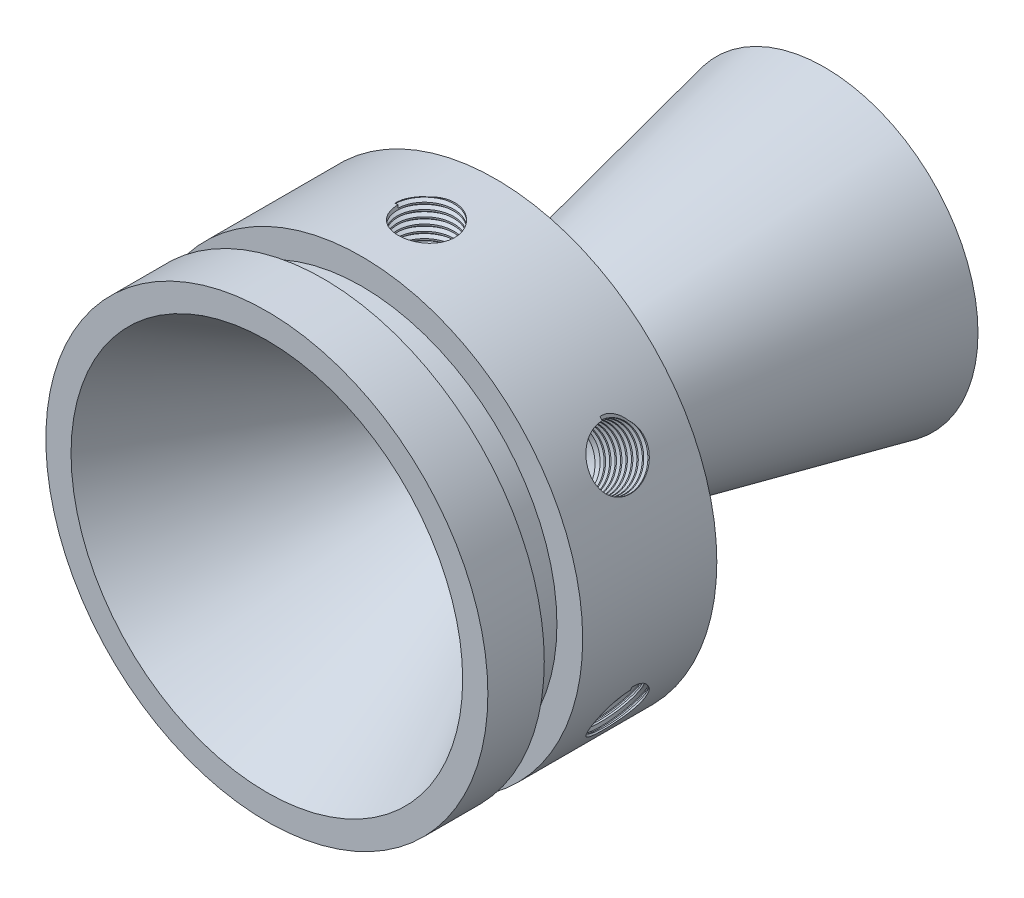
SolidWorks part; units mm, degrees
material "SAE 1018"
ref_plane "Alzado" through (0, 0, 0) normal (0, 0, 1) x (1, 0, 0)
ref_plane "Planta" through (0, 0, 0) normal (0, 1, 0) x (1, 0, 0)
ref_plane "Vista lateral" through (0, 0, 0) normal (1, 0, 0) x (0, 0, -1)
sketch "Croquis2" plane through (0, 0, 0) normal (1, 0, 0) x (0, 0, -1)
  line L0 (-14.0172, 0) -> (56.1534, 0) construction
  line L1 (0, 15.54) -> (17.4731, 5.4519)
  line L3 (0, 15.54) -> (0, 17.54)
  line L4 (0, 17.54) -> (4.476, 17.54)
  line L5 (18.1692, 17.54) -> (18.1692, 8.54)
  line L7 (44.264, 12.1715) -> (44.264, 10.1715)
  line L8 (4.476, 17.54) -> (4.476, 15.4951)
  line L9 (4.476, 15.4951) -> (7.524, 15.4951)
  line L10 (7.524, 15.4951) -> (7.524, 17.54)
  line L11 (7.524, 17.54) -> (18.1692, 17.54)
  line L12 (18.9731, 5.05) -> (19.6437, 5.05)
  line L13 (20.6833, 5.1593) -> (44.264, 10.1715)
  line L15 (20.1692, 7.05) -> (44.264, 12.1715)
  line L16 (19.1692, 7.3661) -> (19.1692, 4.8006) construction
  line L17 (20.1692, 7.05) -> (18.1692, 8.54)
  line L18 (16.3437, 6.104) -> (19.3157, 4.3881) construction
  line L19 (19.0363, 5.05) -> (17.4124, 5.05) construction
  line L20 (19.4766, 5.05) -> (20.8834, 5.05) construction
  line L21 (21.256, 5.281) -> (19.5107, 4.91) construction
  arc A0 (18.9731, 5.05) -> (17.4731, 5.4519) centre (18.9731, 8.05) cw
  arc A1 (19.6437, 5.05) -> (20.6833, 5.1593) centre (19.6437, 10.05) ccw
  point P14 (6, 15.4951)
  point P15 (12.6692, 17.54)
  point P19 (20.1692, 5.05)
  point P23 (18.1692, 5.05)
  point P30 (18.1692, 5.05)
  point P35 (20.1692, 5.05)
  dimension "D14" = 3
  dimension "D15" = 5
  dimension "D2" = 30
  dimension "D4" = 31.08
  dimension "D5" = 20.343
  dimension "D7" = 35.08
  dimension "D8" = 6
  dimension "D11" = 5.5
  dimension "D3" = 2
  dimension "D6" = 10.1
  dimension "D12" = 2
  dimension "D13" = 12
  dimension "D16" = 9
  dimension "D9" = 2.0449
  dimension "D10" = 3.048
revolve "Revolución1" add sketch "Croquis2" angle 360 about L0
ref_plane "Plano1" through (0, 17.54, 0) normal (0, 1, 0) x (1, 0, 0)
sketch "Croquis3" plane through (0, 17.54, 0) normal (0, 1, 0) x (1, 0, 0)
  line L0 (17.54, 18.1692) -> (-17.54, 18.1692) construction
  point P0 (0, 12.6692)
  dimension "D1" = 5.5
hole_wizard "M4 Clearance Hole1" positions "Croquis3" profile "Croquis5" hole size "M4" standard "ANSI Metric"
sketch "Croquis5" plane through (0, 17.54, -12.6692) normal (1, 0, 0) x (0, 0, 1)
  line L0 (0, 0) -> (0, 6.3519)
  line L1 (0, 6.3519) -> (2.25, 5)
  line L2 (2.25, 5) -> (2.25, 0)
  line L5 (2.25, 0) -> (0, 0)
  line L10 (0, 6.3519) -> (-2.25, 5) construction
  line L11 (0, -6.35) -> (0, 107.95) construction
  dimension "Diámetro de taladro" = 4.5
  dimension "Profundidad de taladro" = 5
  dimension "Ángulo de perforador" = 118
thread "Rosca1" pitch 0.5 start angle 0, offset 0, length 4.5, pitch 0.5, diameter 4.5
ref_plane "Plano2" through (-2.25, 17.54, -12.6692) normal (0, 0, 1) x (-1, 0, 0)
sketch "Perfil de rosca1" plane through (-2.25, 17.54, -12.6692) normal (0, 0, 1) x (-1, 0, 0)
  line L0 (0, 0) -> (0, 0.5) construction
  line L1 (0, 0) -> (0.2706, 0.1562)
  line L2 (0.2706, 0.1562) -> (0.2706, 0.2187)
  line L3 (0.2706, 0.2187) -> (0, 0.375)
  line L4 (0.2706, 0.1875) -> (0, 0.1875) construction
  line L11 (0, 0) -> (0, 0.375)
  point P2 (0, 0)
  dimension "Pitch" = 0.5
  dimension "Profile_Angle" = 60
  dimension "Profile_Land" = 0.0625
  dimension "Profile_Height" = 0.2706
pattern_circular "MatrizC1" count 6 over 360 about axis through (0, 0, 14.0172) along (0, 0, 1) of "M4 Clearance Hole1"
pattern_circular "MatrizC2" count 6 over 360 about axis through (0, 0, 14.0172) along (0, 0, 1) of "Rosca1"
equation "\"Dexit\"= 20.343"
equation "\"D5@Croquis2\"=\"Dexit\""
equation "\"DinnerCase\"= 35.08"
equation "\"D7@Croquis2\"=\"DinnerCaseReal\""
equation "\"RadialClearance\"= 0.002pulgadas"
equation "\"DinnerCaseReal\"= \"DinnerCase\" - \"RadialClearance\" * 2"
equation "\"OringXlocation\"= 6"
equation "\"D8@Croquis2\"=\"OringXlocation\""
equation "\"G\"= 0.12pulgadas'O-ring widht gland 0.12<G<0.125 in"
equation "\"D\"= 0.08pulgadas'O-ring depth gland 0.08<D<0.084 in"
equation "\"ScrewXlocation\"= 5.5"
equation "\"D11@Croquis2\"=\"ScrewXlocation\""
equation "\"NozzleBellThickness\"=3"
equation "\"D1@Croquis3\"=\"ScrewXlocation\""
equation "\"DnozzleThroat\"=10.1"
equation "\"D6@Croquis2\"=\"DnozzleThroat\""
equation "\"LengthNozzleThroat\"=2"
equation "\"D3@Croquis2\"=\"LengthNozzleThroat\""
equation "\"OuterNozzleBellThickness\"=2"
equation "\"D12@Croquis2\"=\"OuterNozzleBellThickness\""
equation "\"DivergenceAngle\"=12"
equation "\"D13@Croquis2\"=\"DivergenceAngle\""
equation "\"ConvergenceAngle\"=30"
equation "\"D2@Croquis2\"=\"ConvergenceAngle\""
equation "\"ConvergenceThroatRadius\"= 3"
equation "\"D14@Croquis2\"=\"ConvergenceThroatRadius\""
equation "\"DivergenceThroatRadius\"=5"
equation "\"D15@Croquis2\"=\"DivergenceThroatRadius\""
